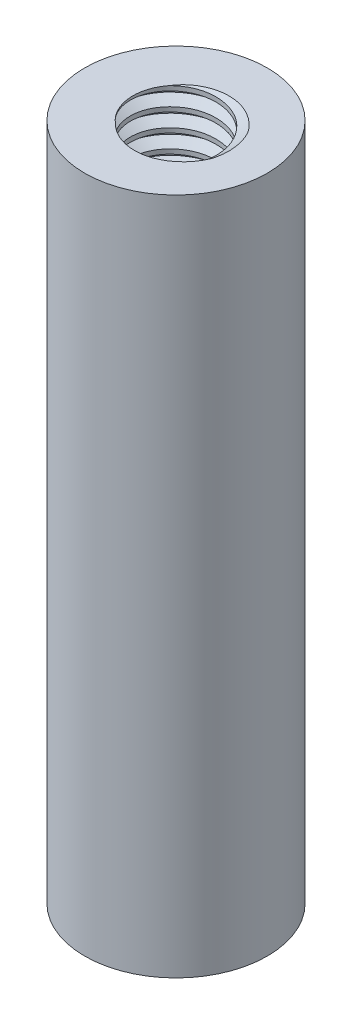
SolidWorks part; units mm, degrees
ref_plane "Front Plane" through (0, 0, 0) normal (0, 0, 1) x (1, 0, 0)
ref_plane "Top Plane" through (0, 0, 0) normal (0, 1, 0) x (1, 0, 0)
ref_plane "Right Plane" through (0, 0, 0) normal (1, 0, 0) x (0, 0, -1)
sketch "Sketch1" plane through (0, 0, 0) normal (0, 1, 0) x (1, 0, 0)
  circle A0 centre (0, 0) radius 3.5
  dimension "D1" = 7
extrude "Boss-Extrude1" add sketch "Sketch1" along normal mid plane 26
sketch "Sketch2" plane through (0, 13, 0) normal (0, 1, 0) x (1, 0, 0)
  circle A0 centre (0, 0) radius 1.65
  dimension "D1" = 3.3
extrude "Cut-Extrude1" cut sketch "Sketch2" against normal blind 6.5
thread "Thread1" pitch 0.7 method cut profile "Thread Profile1" start angle 0, offset 2, length 8, pitch 0.7, diameter 3.3
ref_plane "Plane1" through (-1.65, 15, 0) normal (0, 0, 1) x (-1, 0, 0)
sketch "Thread Profile1" plane through (-1.65, 15, 0) normal (0, 0, 1) x (-1, 0, 0)
  line L0 (0, 0) -> (0, 0.7) construction
  line L1 (0, 0) -> (0.3789, 0.2187)
  line L2 (0.3789, 0.2187) -> (0.3789, 0.3062)
  line L3 (0.3789, 0.3062) -> (0, 0.525)
  line L4 (0.3789, 0.2625) -> (0, 0.2625) construction
  line L11 (0, 0) -> (0, 0.525)
  point P2 (0, 0)
  dimension "Pitch" = 0.7
  dimension "Profile_Angle" = 60
  dimension "Profile_Land" = 0.0875
  dimension "Profile_Height" = 0.3789
mirror "Mirror3" about plane through (0, 0, 0) normal (0, 1, 0) of "Cut-Extrude1"
thread "Thread2" pitch 0.7 method cut profile "Thread Profile2" start angle 0, offset 2, length 8, pitch 0.7, diameter 3.3
ref_plane "Plane2" through (1.65, -15, 0) normal (0, 0, 1) x (1, 0, 0)
sketch "Thread Profile2" plane through (1.65, -15, 0) normal (0, 0, 1) x (1, 0, 0)
  line L0 (0, 0) -> (0, 0.7) construction
  line L1 (0, 0) -> (0.3789, 0.2187)
  line L2 (0.3789, 0.2187) -> (0.3789, 0.3062)
  line L3 (0.3789, 0.3062) -> (0, 0.525)
  line L4 (0.3789, 0.2625) -> (0, 0.2625) construction
  line L11 (0, 0) -> (0, 0.525)
  point P2 (0, 0)
  dimension "Pitch" = 0.7
  dimension "Profile_Angle" = 60
  dimension "Profile_Land" = 0.0875
  dimension "Profile_Height" = 0.3789
